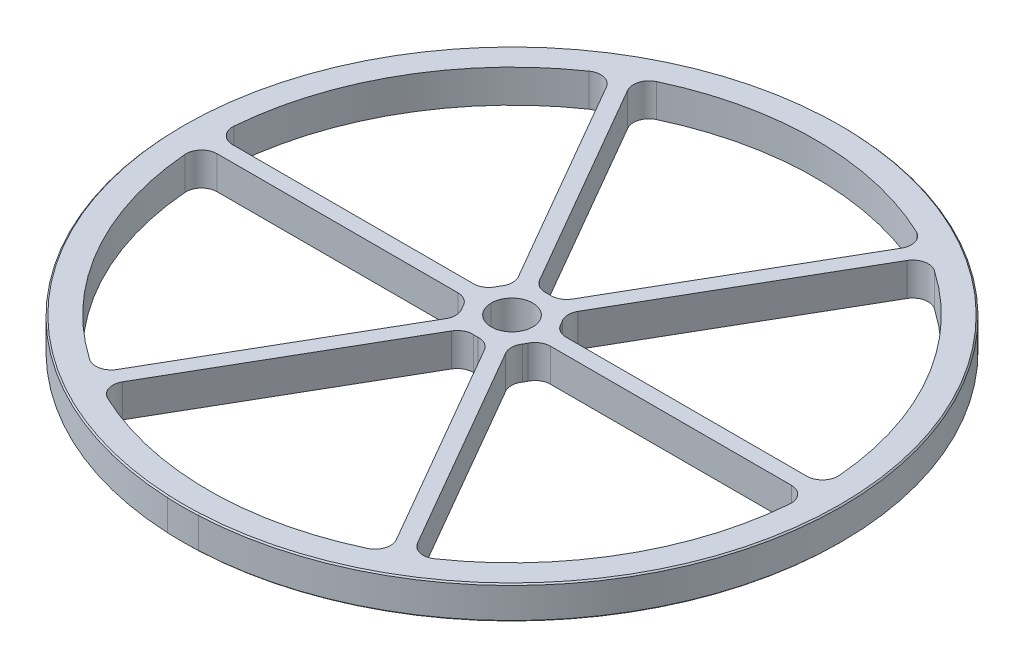
SolidWorks part; units mm, degrees
material "7075-T6, Plate (SS)"
ref_plane "Front Plane" through (0, 0, 0) normal (0, 0, 1) x (1, 0, 0)
ref_plane "Top Plane" through (0, 0, 0) normal (0, 1, 0) x (1, 0, 0)
ref_plane "Right Plane" through (0, 0, 0) normal (1, 0, 0) x (0, 0, -1)
sketch "Sketch1" plane through (0, 0, 0) normal (0, 1, 0) x (1, 0, 0)
  line L0 (0, 0) -> (0, 63.5) construction
  line L2 (-3.1661, 8.4839) -> (-26.3596, 48.6562)
  line L4 (3.1661, 8.4839) -> (26.3596, 48.6562)
  line L11 (5.7642, 6.9839) -> (28.9577, 47.1562)
  line L12 (8.9303, 1.5) -> (55.3173, 1.5)
  line L13 (8.9303, -1.5) -> (55.3173, -1.5)
  line L14 (5.7642, -6.9839) -> (28.9577, -47.1562)
  line L15 (3.1661, -8.4839) -> (26.3596, -48.6562)
  line L16 (-3.1661, -8.4839) -> (-26.3596, -48.6562)
  line L17 (-5.7642, -6.9839) -> (-28.9577, -47.1562)
  line L18 (-8.9303, -1.5) -> (-55.3173, -1.5)
  line L19 (-8.9303, 1.5) -> (-55.3173, 1.5)
  line L20 (-5.7642, 6.9839) -> (-28.9577, 47.1562)
  circle A0 centre (0, 0) radius 63.5
  circle A1 centre (0, 0) radius 4
  arc A2 (0.3976, 6.9887) -> (-0.3976, 6.9887) centre (0, 0) ccw
  arc A3 (25.0459, 52.8673) -> (-25.0459, 52.8673) centre (0, 0) ccw
  arc A20 (-0.3976, 6.9887) -> (-3.1661, 8.4839) centre (-0.568, 9.9839) cw
  arc A21 (0.3976, 6.9887) -> (3.1661, 8.4839) centre (0.568, 9.9839) ccw
  arc A22 (25.0459, 52.8673) -> (26.3596, 48.6562) centre (23.7615, 50.1562) cw
  arc A23 (-25.0459, 52.8673) -> (-26.3596, 48.6562) centre (-23.7615, 50.1562) ccw
  arc A32 (6.2512, 3.15) -> (5.8536, 3.8387) centre (0, 0) ccw
  arc A33 (6.2512, 3.15) -> (8.9303, 1.5) centre (8.9303, 4.5) ccw
  arc A34 (5.8536, 3.8387) -> (5.7642, 6.9839) centre (8.3623, 5.4839) cw
  arc A35 (33.2615, 48.1241) -> (28.9577, 47.1562) centre (31.5557, 45.6562) ccw
  arc A36 (58.3074, 4.7432) -> (33.2615, 48.1241) centre (0, 0) ccw
  arc A37 (58.3074, 4.7432) -> (55.3173, 1.5) centre (55.3173, 4.5) cw
  arc A38 (5.8536, -3.8387) -> (6.2512, -3.15) centre (0, 0) ccw
  arc A39 (5.8536, -3.8387) -> (5.7642, -6.9839) centre (8.3623, -5.4839) ccw
  arc A40 (6.2512, -3.15) -> (8.9303, -1.5) centre (8.9303, -4.5) cw
  arc A41 (58.3074, -4.7432) -> (55.3173, -1.5) centre (55.3173, -4.5) ccw
  arc A42 (33.2615, -48.1241) -> (58.3074, -4.7432) centre (0, 0) ccw
  arc A43 (33.2615, -48.1241) -> (28.9577, -47.1562) centre (31.5557, -45.6562) cw
  arc A44 (-0.3976, -6.9887) -> (0.3976, -6.9887) centre (0, 0) ccw
  arc A45 (-0.3976, -6.9887) -> (-3.1661, -8.4839) centre (-0.568, -9.9839) ccw
  arc A46 (0.3976, -6.9887) -> (3.1661, -8.4839) centre (0.568, -9.9839) cw
  arc A47 (25.0459, -52.8673) -> (26.3596, -48.6562) centre (23.7615, -50.1562) ccw
  arc A48 (-25.0459, -52.8673) -> (25.0459, -52.8673) centre (0, 0) ccw
  arc A49 (-25.0459, -52.8673) -> (-26.3596, -48.6562) centre (-23.7615, -50.1562) cw
  arc A50 (-6.2512, -3.15) -> (-5.8536, -3.8387) centre (0, 0) ccw
  arc A51 (-6.2512, -3.15) -> (-8.9303, -1.5) centre (-8.9303, -4.5) ccw
  arc A52 (-5.8536, -3.8387) -> (-5.7642, -6.9839) centre (-8.3623, -5.4839) cw
  arc A53 (-33.2615, -48.1241) -> (-28.9577, -47.1562) centre (-31.5557, -45.6562) ccw
  arc A54 (-58.3074, -4.7432) -> (-33.2615, -48.1241) centre (0, 0) ccw
  arc A55 (-58.3074, -4.7432) -> (-55.3173, -1.5) centre (-55.3173, -4.5) cw
  arc A56 (-5.8536, 3.8387) -> (-6.2512, 3.15) centre (0, 0) ccw
  arc A57 (-5.8536, 3.8387) -> (-5.7642, 6.9839) centre (-8.3623, 5.4839) ccw
  arc A58 (-6.2512, 3.15) -> (-8.9303, 1.5) centre (-8.9303, 4.5) cw
  arc A59 (-58.3074, 4.7432) -> (-55.3173, 1.5) centre (-55.3173, 4.5) ccw
  arc A60 (-33.2615, 48.1241) -> (-58.3074, 4.7432) centre (0, 0) ccw
  arc A61 (-33.2615, 48.1241) -> (-28.9577, 47.1562) centre (-31.5557, 45.6562) cw
  point P44 (-2.1197, 6.6714)
  point P47 (2.1197, 6.6714)
  point P50 (27.9413, 51.3958)
  point P53 (-27.9413, 51.3958)
  point P72 (0, 0)
  dimension "D1" = 127
  dimension "D2" = 8
  dimension "D3" = 6
  dimension "D4" = 5
  dimension "D7" = 3
  dimension "D8" = 3
  dimension "D6" = 3
  dimension "D5" = 3
extrude "Boss-Extrude3" add sketch "Sketch1" along normal blind 6.35
ref_axis "Axis1" through (0, 6.35, 0) along (0, -1, 0)
ref_plane "Plane3" [suppressed] through (0, 0, 0) normal (0.2756, 0, 0.9613) x (0.9613, 0, -0.2756)
split line "Split Line1" [suppressed]
sketch "Sketch2" [suppressed] plane through (0, 6.35, 0) normal (0, 1, 0) x (1, 0, 0)
  line L0 (0, 0) -> (0, -38.1)
  circle A0 centre (0, 0) radius 38.1 construction
ref_plane "Plane4" [suppressed] through (0, 0, 0) normal (0, 0, 1) x (1, 0, 0)
ref_plane "Plane5" [suppressed] through (0, 0, 38.1) normal (0, 0, 1) x (1, 0, 0)
sketch "Sketch5" [suppressed] plane through (0, 0, 38.1) normal (0, 0, 1) x (1, 0, 0)
  line L5 (38.1, 6.35) -> (-38.1, 6.35) construction
  line L6 (-3, 6.35) -> (3, 6.35)
  line L7 (-3, 6.35) -> (-3, 0)
  line L8 (-3, 0) -> (3, 0)
  line L9 (3, 6.35) -> (3, 0)
  line L10 (-38.1, 0) -> (38.1, 0) construction
  dimension "D1" = 6
split line "Split Line2" [suppressed]
split line "Split Line3" [suppressed]
sketch "Sketch6" plane through (0, 6.35, 0) normal (0, 1, 0) x (1, 0, 0)
  line L0 (0, 0) -> (0, -58.5)
  arc A1 (-25.0459, -52.8673) -> (25.0459, -52.8673) centre (0, 0) ccw construction
ref_plane "Plane7" through (0, 0, 0) normal (0, 0, 1) x (1, 0, 0)
ref_plane "Plane8" through (0, 0, 63.5) normal (0, 0, 1) x (1, 0, 0)
sketch "Sketch7" plane through (0, 0, 63.5) normal (0, 0, 1) x (1, 0, 0)
  line L1 (-3, 6.35) -> (3, 6.35)
  line L2 (-3, 6.35) -> (-3, 0)
  line L3 (-3, 0) -> (3, 0)
  line L4 (3, 6.35) -> (3, 0)
  dimension "D1" = 6.35
  dimension "D2" = 6
split line "Split Line4"
split line "Split Line5"
chamfer "Chamfer2" distance 0.25 angle 45 8 edges at (63.5, 6.35, 0) (0, 6.35, -63.5) (-63.5, 6.35, 0) (0, 6.35, 63.5) (63.5, 0, 0) (0, 0, 63.5) (-63.5, 0, 0) (0, 0, -63.5)
sketch "Sketch9" [suppressed] plane through (0, 6.35, 0) normal (0, 1, 0) x (1, 0, 0)
  circle A7 centre (0, 0) radius 39.25
  circle A8 centre (0, 0) radius 39.25
  circle A10 centre (0, 0) radius 3.5
  circle A11 centre (0, 0) radius 3.5
  circle A13 centre (0, 0) radius 38.25
  circle A14 centre (0, 0) radius 38.25
  circle A16 centre (0, 0) radius 6.5
  circle A17 centre (0, 0) radius 6.5
  circle M6 centre (0, 0) radius 38.25
  circle M7 centre (0, 0) radius 6.5
  dimension "D1" = 1
  dimension "D2" = 3
  dimension "D3" = 0
  dimension "D4" = 0
extrude "Boss-Extrude4" [suppressed] add sketch "Sketch9" against normal up to surface (6.35 mm away) contours A11 M7 | A8 M6
